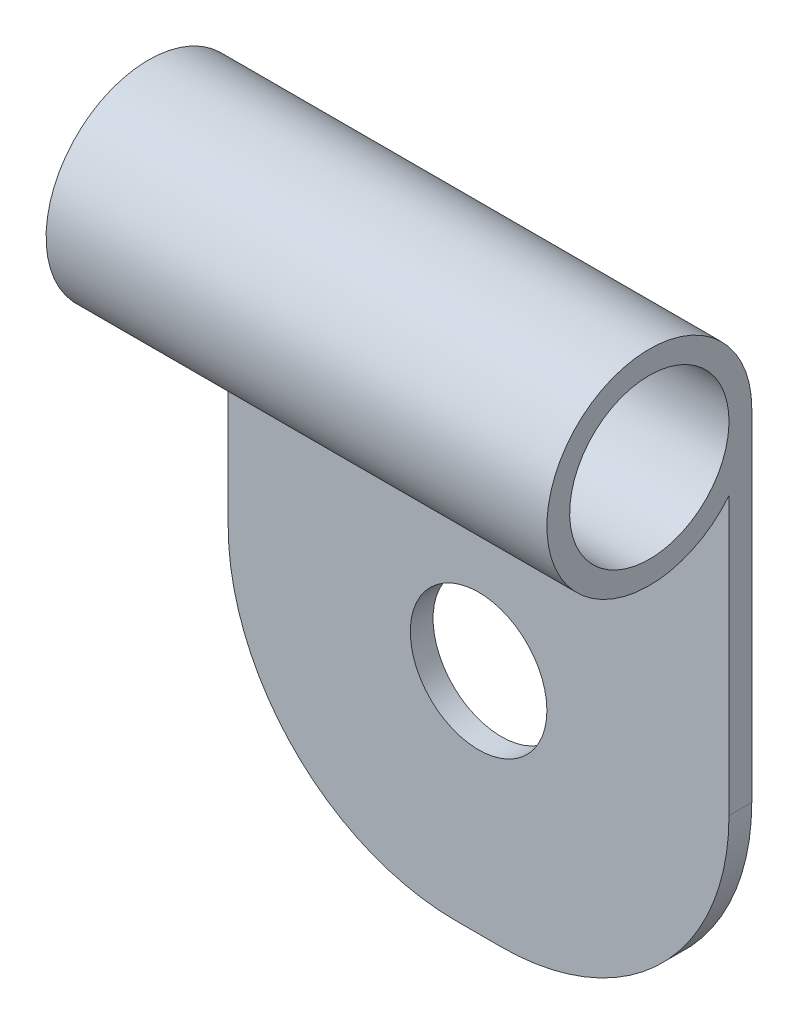
SolidWorks part; units mm, degrees
material "Nickel"
ref_plane "Plane1" through (0, 0, 0) normal (0, 0, 1) x (1, 0, 0)
ref_plane "Plane2" through (0, 0, 0) normal (0, 1, 0) x (1, 0, 0)
ref_plane "Plane3" through (0, 0, 0) normal (1, 0, 0) x (0, 0, -1)
sketch "Sketch1" plane through (0, 0, 0) normal (0, 0, 1) x (1, 0, 0)
  line L0 (-14.7053, 0) -> (16.1758, 0) construction
  line L1 (0, -10) -> (0, 15) construction
  line L2 (-1, -10) -> (1, -10)
  line L3 (11, 15) -> (11, 0)
  line L4 (11, 15) -> (-11, 15)
  line L5 (-11, 15) -> (-11, 0)
  circle A0 centre (0, 0) radius 3
  arc A1 (1, -10) -> (11, 0) centre (1, 0) ccw
  arc A2 (-1, -10) -> (-11, 0) centre (-1, 0) cw
  dimension "D1" = 6
  dimension "D2" = 10
  dimension "D3" = 11
  dimension "D4" = 15
extrude "Extrude1" add sketch "Sketch1" along normal blind 1
sketch "Sketch2" plane through (11, 0, 0) normal (1, 0, 0) x (0, 0, -1)
  line L0 (-1, 15) -> (-7.6228, 15) construction
  circle A0 centre (-4.5, 15) radius 4.5
  circle A1 centre (-4.5, 15) radius 3.5
  dimension "D1" = 7
extrude "Extrude2" add sketch "Sketch2" against normal through all
sketch "Sketch3" plane through (11, 0, 0) normal (1, 0, 0) x (0, 0, -1)
  point P0 (-4.5, 15)
sketch "Sketch4" plane through (-11, 0, 0) normal (-1, 0, 0) x (0, 0, 1)
  point P0 (4.5, 15)
other "RPoint1"
ref_axis "Axis1" through (-6, 15, 4.5) along (-1, 0, 0)
other "RPoint2"
ref_axis "Axis2" through (6, 15, 4.5) along (1, 0, 0)
ref_axis "Clip Axis" through (11, 15, 4.5) along (-1, 0, 0)
sketch "FilterSketch" plane through (11, 0, 0) normal (1, 0, 0) x (0, 0, -1)
  circle A0 centre (-4.5, 15) radius 3 construction
  circle A1 centre (-4.5, 15) radius 0.05 construction
  circle A2 centre (-4.5, 15) radius 3.25 construction
  dimension "NominalDiameter" = 6
  dimension "InnerDiameter" = 0.1
  dimension "OuterDiameter" = 6.5
ref_axis "Axis of Rotation" through (0, 0, 1) along (0, 0, -1)
